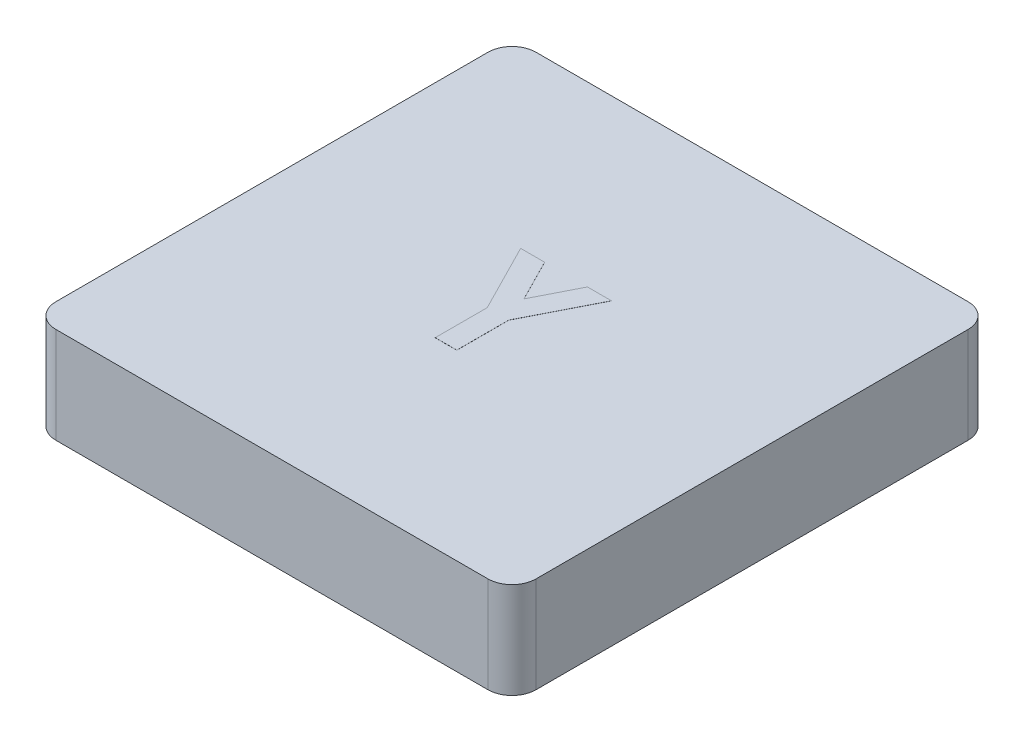
SolidWorks part; units mm, degrees
ref_plane "Front Plane" through (0, 0, 0) normal (0, 0, 1) x (1, 0, 0)
ref_plane "Top Plane" through (0, 0, 0) normal (0, 1, 0) x (1, 0, 0)
ref_plane "Right Plane" through (0, 0, 0) normal (1, 0, 0) x (0, 0, -1)
sketch "Sketch1" plane through (0, 0, 0) normal (0, 1, 0) x (1, 0, 0)
  line L0 (0, 0) -> (12.7, 0)
  line L1 (12.7, 0) -> (12.7, 12.7)
  line L2 (12.7, 12.7) -> (0, 12.7)
  line L3 (0, 12.7) -> (0, 0)
  dimension "D1" = 12.7
  dimension "D2" = 12.7
extrude "Boss-Extrude1" add sketch "Sketch1" along normal blind 2.54
fillet "Fillet1" radius 0.635 4 edges at (0, 1.27, -12.7) (12.7, 1.27, -12.7) (12.7, 1.27, 0) (0, 1.27, 0)
shell "Shell1" thickness 0.635 removed face at (6.35, 0, -6.35)
sketch "Sketch2" plane through (0, 1.905, 0) normal (0, -1, 0) x (-1, 0, 0)
  line L0 (-0.635, 6.35) -> (-12.065, 6.35) construction
  line L1 (-0.635, 12.065) -> (-0.635, 0.635) construction
  line L2 (-12.065, 0.635) -> (-12.065, 12.065) construction
  line L3 (-6.35, 0.635) -> (-6.35, 12.065) construction
  line L4 (-0.635, 0.635) -> (-12.065, 0.635) construction
  line L5 (-12.065, 12.065) -> (-0.635, 12.065) construction
  circle A0 centre (-6.35, 6.35) radius 2.54
  dimension "D1" = 5.08
extrude "Boss-Extrude2" add sketch "Sketch2" along normal up to surface (1.905 mm away) up to face at (6.35, 0, -6.35)
sketch "Sketch3" plane through (0, 2.54, 0) normal (0, 1, 0) x (1, 0, 0)
  line L0 (0, 12.065) -> (0, 0.635) construction
  line L1 (0.635, 0) -> (12.065, 0) construction
  text T0 "<b>Y</b>"
  point P1 (0, 0)
  dimension "D1" = 4.826
  dimension "D2" = 4.826
extrude "Boss-Extrude3" add sketch "Sketch3" along normal blind 0.0025
